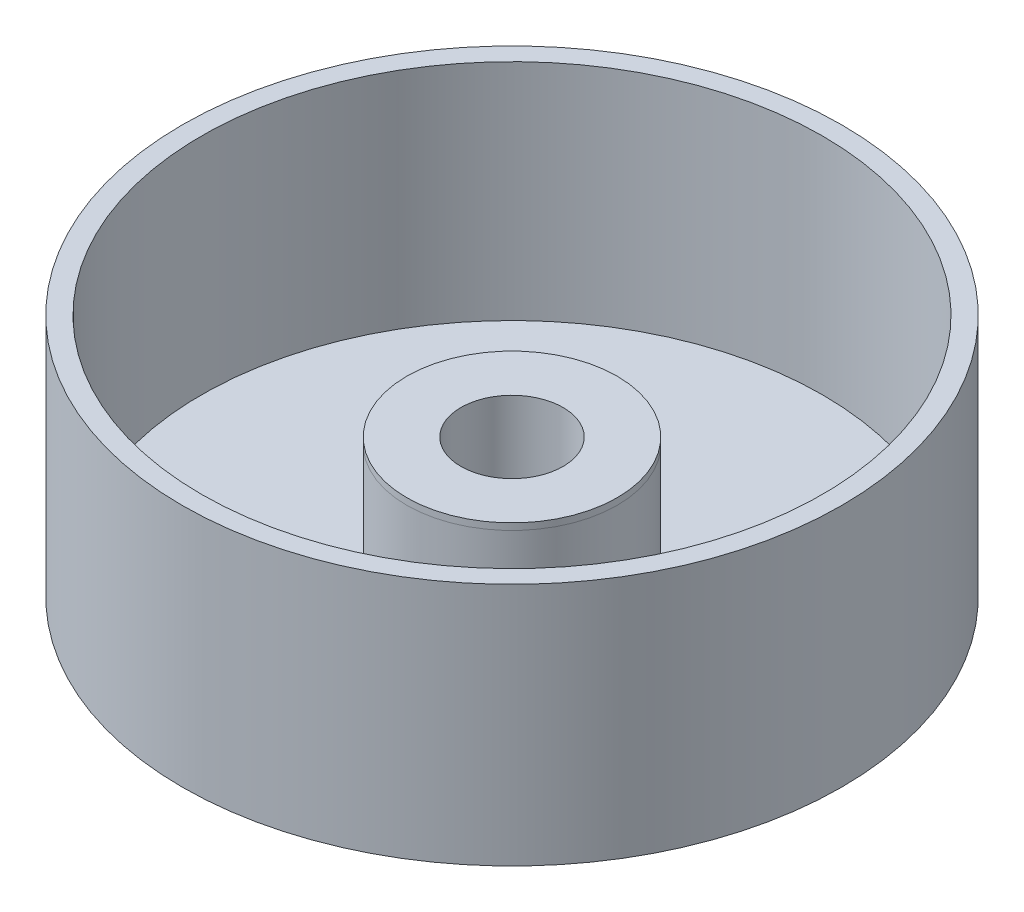
SolidWorks part; units mm, degrees
ref_plane "Front Plane" through (0, 0, 0) normal (0, 0, 1) x (1, 0, 0)
ref_plane "Top Plane" through (0, 0, 0) normal (0, 1, 0) x (1, 0, 0)
ref_plane "Right Plane" through (0, 0, 0) normal (1, 0, 0) x (0, 0, -1)
sketch "Sketch1" plane through (0, 0, 0) normal (0, 1, 0) x (1, 0, 0)
  circle A0 centre (0, 0) radius 15.958
extrude "ShaftHolderNearMotor" add sketch "Sketch1" along normal blind 1
sketch "Sketch2" plane through (0, 1, 0) normal (0, 1, 0) x (1, 0, 0)
  circle A0 centre (0, 0) radius 3.4
extrude "Cut-Extrude1" cut sketch "Sketch2" against normal blind 16.85 contours A0
ref_axis "Axis1" through (0, 0, 0) along (0, 1, 0)
sketch "Sketch10" plane through (0, 0, 0) normal (0, -1, 0) x (1, 0, 0)
  circle A0 centre (0, 0) radius 50
extrude "Boss-Extrude4" add sketch "Sketch10" along normal blind 20
sketch "Sketch11" plane through (0, 0, 0) normal (0, 1, 0) x (1, 0, 0)
  line L1 (31.7817, 38.8528) -> (14.4942, 48.0577) construction
  line L2 (14.4942, 48.0577) -> (-5, 49.9462) construction
  line L3 (-5, 49.9462) -> (-23.733, 44.2308) construction
  line L4 (-23.733, 44.2308) -> (-38.8528, 31.7817) construction
  line L5 (-38.8528, 31.7817) -> (-48.0577, 14.4942) construction
  line L6 (-48.0577, 14.4942) -> (-49.9462, -5) construction
  line L7 (-49.9462, -5) -> (-44.2308, -23.733) construction
  line L8 (-44.2308, -23.733) -> (-31.7817, -38.8528) construction
  line L9 (-31.7817, -38.8528) -> (-14.4942, -48.0577) construction
  line L10 (-14.4942, -48.0577) -> (5, -49.9462) construction
  line L11 (5, -49.9462) -> (23.733, -44.2308) construction
  line L12 (23.733, -44.2308) -> (38.8528, -31.7817) construction
  line L13 (38.8528, -31.7817) -> (48.0577, -14.4942) construction
  line L14 (48.0577, -14.4942) -> (49.9462, 5) construction
  line L15 (49.9462, 5) -> (44.2308, 23.733) construction
  line L16 (44.2308, 23.733) -> (31.7817, 38.8528) construction
  circle A0 centre (0, 0) radius 49.2313 construction
  circle A1 centre (5, -49.9462) radius 5
  circle A2 centre (-14.4942, -48.0577) radius 5
  circle A3 centre (-31.7817, -38.8528) radius 5
  circle A4 centre (-44.2308, -23.733) radius 5
  circle A5 centre (-49.9462, -5) radius 5
  circle A6 centre (-48.0577, 14.4942) radius 5
  circle A7 centre (-38.8528, 31.7817) radius 5
  circle A8 centre (-23.733, 44.2308) radius 5
  circle A9 centre (-5, 49.9462) radius 5
  circle A10 centre (14.4942, 48.0577) radius 5
  circle A11 centre (31.7817, 38.8528) radius 5
  circle A12 centre (44.2308, 23.733) radius 5
  circle A13 centre (49.9462, 5) radius 5
  circle A14 centre (48.0577, -14.4942) radius 5
  circle A15 centre (38.8528, -31.7817) radius 5
  circle A16 centre (23.733, -44.2308) radius 5
sketch "Sketch12" plane through (0, 0, 0) normal (0, 1, 0) x (1, 0, 0)
  circle A0 centre (0, 0) radius 47.0828
  circle A1 centre (0, 0) radius 15.9579
extrude "CutToRemveExcessMaterial" cut sketch "Sketch12" against normal offset from surface (17 mm away) 3 up to face at (0, -20, -50)
sketch "Sketch13" plane through (0, 0, 0) normal (0, 1, 0) x (1, 0, 0)
  circle A0 centre (0, 0) radius 47.0828
  circle A1 centre (0, 0) radius 50
extrude "Boss-Extrude5" add sketch "Sketch13" along normal blind 17
ref_plane "Plane4" through (-0.571, 0, -49.9967) normal (-0.0114, 0, -0.9999) x (-0.9999, 0, 0.0114)
ref_plane "Plane5" through (-27.4359, 0, -41.8004) normal (-0.5487, 0, -0.836) x (-0.836, 0, 0.5487)
sketch "Sketch17" plane through (-0.571, 0, -49.9967) normal (-0.0114, 0, -0.9999) x (-0.9999, 0, 0.0114)
  line L1 (-6.9779, 26.3682) -> (19.0025, 26.3682)
sketch "Sketch18" plane through (-27.4359, 0, -41.8004) normal (-0.5487, 0, -0.836) x (-0.836, 0, 0.5487)
  line L1 (2.3429, -8.8145) -> (-7.3736, -8.8145)
  line L2 (2.3429, -8.8145) -> (2.3429, -36.514)
  line L3 (2.3429, -36.514) -> (-7.3736, -36.514)
  line L4 (-7.3736, -8.8145) -> (-7.3736, -36.514)
ref_plane "Plane6" through (18.6054, 0, -46.4095) normal (0.3721, 0, -0.9282) x (-0.9282, 0, -0.3721)
ref_plane "Plane7" through (34.9493, 0, -35.7568) normal (0.699, 0, -0.7151) x (-0.7151, 0, -0.699)
ref_plane "Plane8" through (45.9725, 0, -19.6605) normal (0.9194, 0, -0.3932) x (-0.3932, 0, -0.9194)
ref_plane "Plane9" through (49.1178, 0, -9.3511) normal (0.9824, 0, -0.187) x (-0.187, 0, -0.9824)
ref_plane "Plane10" through (46.4095, 0, 18.6054) normal (0.9282, 0, 0.3721) x (0.3721, 0, -0.9282)
ref_plane "Plane11" through (35.7568, 0, 34.9493) normal (0.7151, 0, 0.699) x (0.699, 0, -0.7151)
ref_plane "Plane12" through (9.3511, 0, 49.1178) normal (0.187, 0, 0.9824) x (0.9824, 0, -0.187)
ref_plane "Plane13" through (-28.1193, 0, 41.3438) normal (-0.5624, 0, 0.8269) x (0.8269, 0, 0.5624)
ref_plane "Plane14" through (-49.1178, 0, 9.3511) normal (-0.9824, 0, 0.187) x (0.187, 0, 0.9824)
ref_plane "Plane15" through (-41.3438, 0, -28.1193) normal (-0.8269, 0, -0.5624) x (-0.5624, 0, 0.8269)
sketch "Sketch19" plane through (9.3511, 0, 49.1178) normal (0.187, 0, 0.9824) x (0.9824, 0, -0.187)
  circle A0 centre (-6.5538, -15.0444) radius 12
sketch "Sketch20" plane through (35.7568, 0, 34.9493) normal (0.7151, 0, 0.699) x (0.699, 0, -0.7151)
  circle A0 centre (3.5584, 19.4292) radius 12
sketch "Sketch21" plane through (49.1178, 0, -9.3511) normal (0.9824, 0, -0.187) x (-0.187, 0, -0.9824)
  circle A0 centre (-4.7912, -19.2219) radius 10
sketch "Sketch22" plane through (34.9493, 0, -35.7568) normal (0.699, 0, -0.7151) x (-0.7151, 0, -0.699)
  circle A0 centre (5.4277, 18.4908) radius 12.5535
sketch "Sketch23" plane through (-0.571, 0, -49.9967) normal (-0.0114, 0, -0.9999) x (-0.9999, 0, 0.0114)
  circle A0 centre (4.5252, -20.0178) radius 11.9653
sketch "Sketch25" plane through (-41.3438, 0, -28.1193) normal (-0.8269, 0, -0.5624) x (-0.5624, 0, 0.8269)
  circle A0 centre (-2.6498, 18.6432) radius 9.6297
sketch "Sketch26" plane through (-49.1178, 0, 9.3511) normal (-0.9824, 0, 0.187) x (0.187, 0, 0.9824)
  circle A0 centre (-4.4977, -19.1264) radius 15.0124
sketch "Sketch27" plane through (-28.1193, 0, 41.3438) normal (-0.5624, 0, 0.8269) x (0.8269, 0, 0.5624)
  circle A0 centre (-2.2875, 17.6222) radius 11.8547
sketch "Sketch28" plane through (0, 0, 0) normal (0, -1, 0) x (1, 0, 0)
  line L1 (19.8832, 9.4042) -> (21.6, 9.4042)
  line L2 (19.8832, 9.4042) -> (19.8832, -8.7683)
  line L3 (19.8832, -8.7683) -> (21.6, -8.7683)
  line L4 (21.6, 9.4042) -> (21.6, -8.7683)
sketch "Sketch30" plane through (0, 1, 0) normal (0, 1, 0) x (1, 0, 0)
  circle A0 centre (0, 0) radius 3.4
  circle A1 centre (0, 0) radius 8.7876
sketch "Sketch31" plane through (0, 1, 0) normal (0, 1, 0) x (1, 0, 0)
  circle A0 centre (0, 0) radius 26.3365
sketch "Sketch32" plane through (0, 1, 0) normal (0, 1, 0) x (1, 0, 0)
  circle A0 centre (0, 0) radius 7.75
extrude "Cut-Extrude2" cut sketch "Sketch32" against normal through all
